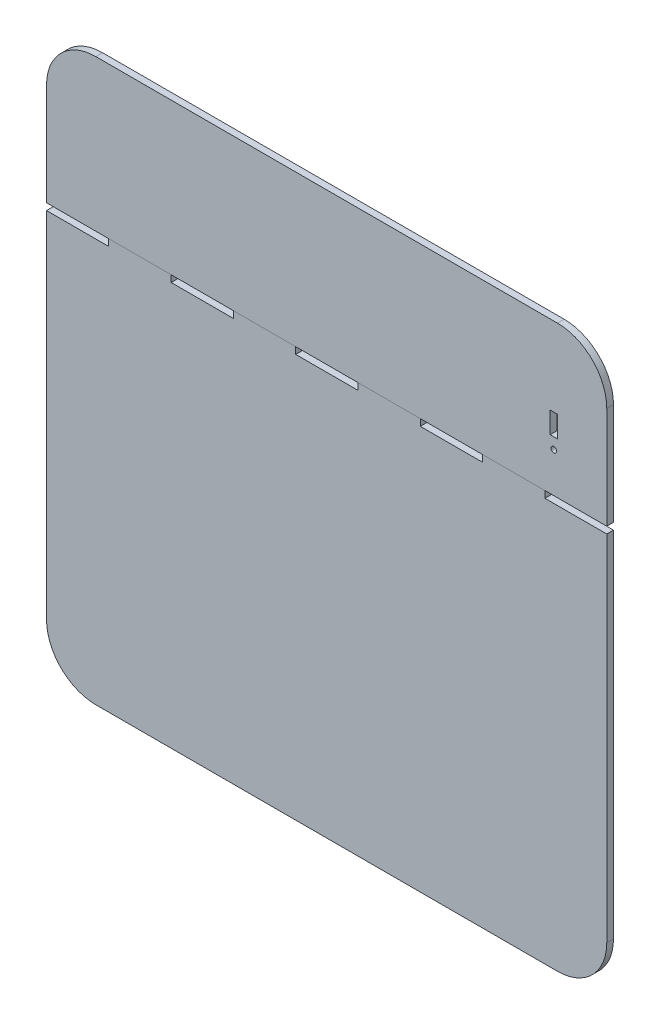
SolidWorks part; units mm, degrees
material "Pine"
ref_plane "Front Plane" through (0, 0, 0) normal (0, 0, 1) x (1, 0, 0)
ref_plane "Top Plane" through (0, 0, 0) normal (0, 1, 0) x (1, 0, 0)
ref_plane "Right Plane" through (0, 0, 0) normal (1, 0, 0) x (0, 0, -1)
sketch "Sketch1" plane through (0, 0, 0) normal (0, 0, 1) x (1, 0, 0)
  line L1 (0, 0) -> (500, 0)
  line L2 (0, 0) -> (0, 501)
  line L3 (0, 501) -> (500, 501)
  line L4 (500, 0) -> (500, 501)
  dimension "D1" = 500
  dimension "D2" = 501
extrude "Boss-Extrude1" add sketch "Sketch1" along normal blind 6
fillet "Fillet1" radius 44 4 edges at (0, 0, 3) (0, 501, 3) (500, 0, 3) (500, 501, 3)
sketch "Sketch2" plane through (0, 0, 0) normal (0, 0, -1) x (-1, 0, 0)
  line L0 (-456, 501) -> (-44, 501) construction
  line L1 (0, 360) -> (-55.5, 360)
  line L2 (0, 360) -> (0, 366)
  line L3 (0, 366) -> (-55.5, 366)
  line L4 (-55.5, 360) -> (-55.5, 366)
  line L5 (0, 457) -> (0, 44) construction
  dimension "D1" = 135
  dimension "D2" = 6
  dimension "D3" = 0
  dimension "D4" = 55.5
extrude "Cut-Extrude1" cut sketch "Sketch2" against normal blind 10
pattern_linear "LPattern1" count 5 spacing 111.2 along (1, 0, 0) of "Cut-Extrude1"
sketch "Sketch4" plane through (0, 0, 0) normal (0, 0, -1) x (-1, 0, 0)
  line L0 (-456, 501) -> (-44, 501) construction
  line L1 (-456, 430.5) -> (-449.5, 430.5)
  line L2 (-456, 430.5) -> (-456, 411.5)
  line L3 (-456, 411.5) -> (-449.5, 411.5)
  line L4 (-449.5, 430.5) -> (-449.5, 411.5)
  point P5 (-449.5, 421)
  dimension "D1" = 19
  dimension "D2" = 6.5
  dimension "D3" = 0
  dimension "D4" = 80
extrude "Cut-Extrude3" cut sketch "Sketch4" against normal blind 10
sketch "Sketch3" plane through (0, 0, 0) normal (0, 0, -1) x (-1, 0, 0)
  line L0 (-456, 411.5) -> (-449.5, 411.5) construction
  circle A0 centre (-452.75, 401.5) radius 2.5
  point P6 (-452.75, 411.5)
  dimension "D1" = 0
  dimension "D3" = 5
  dimension "D2" = 10
extrude "Cut-Extrude2" cut sketch "Sketch3" against normal blind 10
sketch "Sketch5" plane through (0, 0, 6) normal (0, 0, 1) x (1, 0, 0)
  line L0 (0, 366) -> (500, 366)
  line L1 (0, 366) -> (55.5, 366) construction
  line L2 (444.8, 366) -> (500, 366) construction
split "Split1" trim tools "Sketch5" bodies to split 104 resulting bodies 106 107
